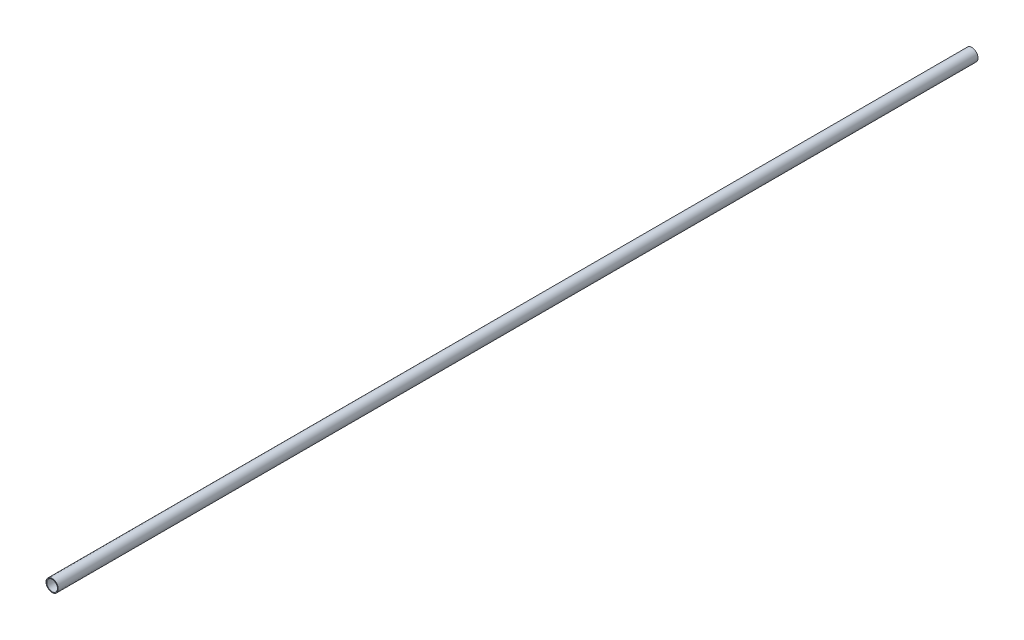
SolidWorks part; units mm, degrees
material "1060 Alloy"
ref_plane "Front Plane" through (0, 0, 0) normal (0, 0, 1) x (1, 0, 0)
ref_plane "Top Plane" through (0, 0, 0) normal (0, 1, 0) x (1, 0, 0)
ref_plane "Right Plane" through (0, 0, 0) normal (1, 0, 0) x (0, 0, -1)
sketch "Sketch1" plane through (0, 0, 0) normal (0, 0, 1) x (1, 0, 0)
  circle A0 centre (0, 0) radius 3.5
  circle A1 centre (0, 0) radius 4
  dimension "D1" = 7
  dimension "D2" = 8
extrude "Boss-Extrude1" add sketch "Sketch1" along normal mid plane 600
